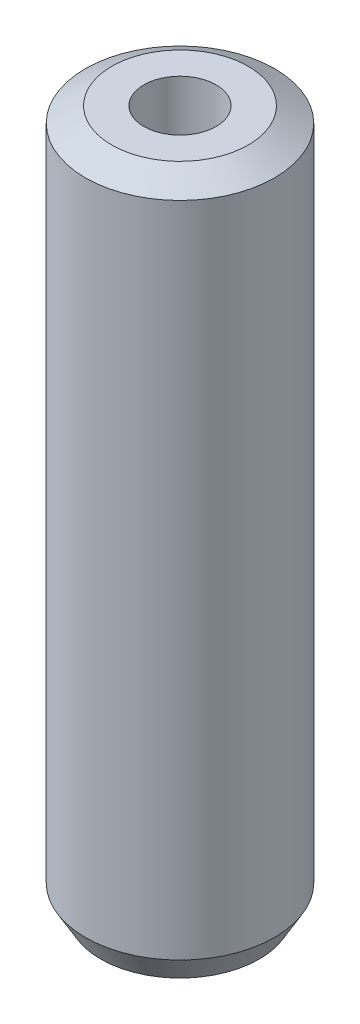
SolidWorks part; units mm, degrees
ref_plane "Front Plane" through (0, 0, 0) normal (0, 0, 1) x (1, 0, 0)
ref_plane "Top Plane" through (0, 0, 0) normal (0, 1, 0) x (1, 0, 0)
ref_plane "Right Plane" through (0, 0, 0) normal (1, 0, 0) x (0, 0, -1)
sketch "Sketch1" plane through (0, 0, 0) normal (0, 1, 0) x (1, 0, 0)
  circle A0 centre (0, 0) radius 30
  dimension "SHAFT_OD" = 60
extrude "Boss-Extrude1" add sketch "Sketch1" along normal blind 221.8175
sketch "Sketch2" plane through (0, 0, 0) normal (0, 1, 0) x (1, 0, 0)
  circle A0 centre (0, 0) radius 11.4549
  dimension "BORE_D" = 22.9098
extrude "Cut-Extrude1" cut sketch "Sketch2" along normal through all
chamfer "Chamfer1" distance 4.8274 angle 60 2 edges at (0, 221.8175, 30) (0, 0, 30) first distance on face at (0, 221.8175, 30) first distance on face at (0, 0, 11.4549)
